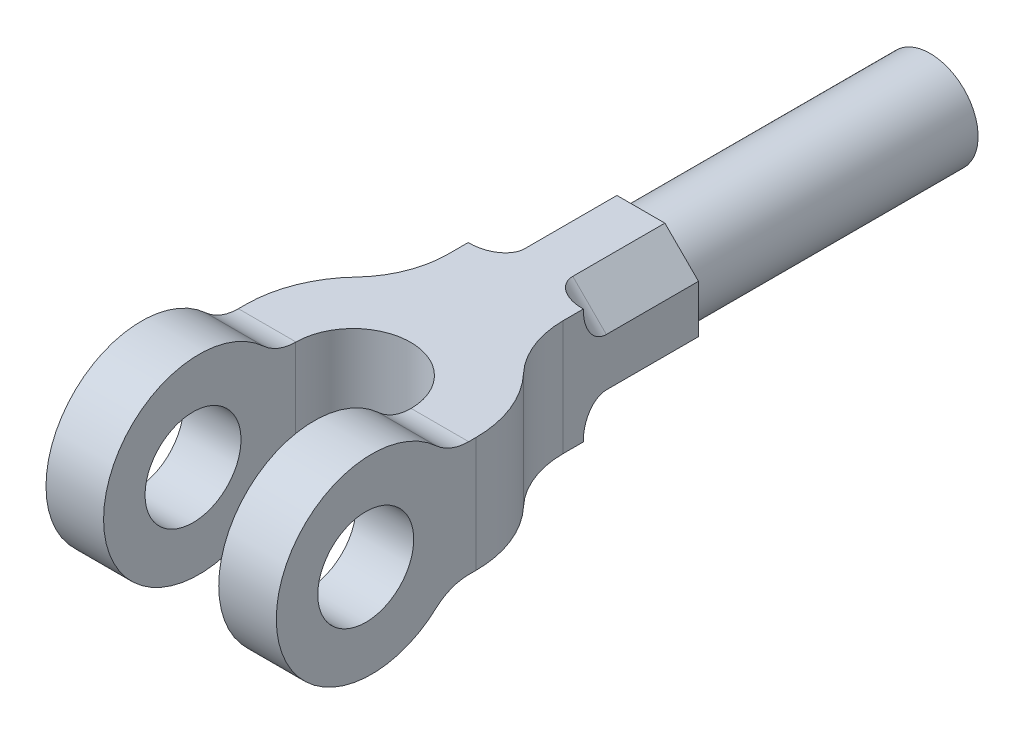
SolidWorks part; units mm, degrees
ref_plane "Front Plane" through (0, 0, 0) normal (0, 0, 1) x (1, 0, 0)
ref_plane "Top Plane" through (0, 0, 0) normal (0, 1, 0) x (1, 0, 0)
ref_plane "Right Plane" through (0, 0, 0) normal (1, 0, 0) x (0, 0, -1)
sketch "Sketch2" plane through (0, 0, 0) normal (0, 1, 0) x (1, 0, 0)
  line L1 (0, 0) -> (-120, 0)
  line L2 (0, 0) -> (0, 250)
  line L3 (0, 250) -> (-120, 250)
  line L4 (-120, 0) -> (-120, 250)
  line L5 (0, 0) -> (-120, 250) construction
  line L6 (0, 250) -> (-120, 0) construction
  point P4 (-98.6047, 60.2326)
  dimension "D1" = 250
  dimension "D2" = 120
extrude "Boss-Extrude1" add sketch "Sketch2" along normal mid plane 100
sketch "Sketch3" plane through (0, 50, 0) normal (0, 1, 0) x (1, 0, 0)
  line L0 (-60, 249.7647) -> (-60, -1.0314) construction
  line L1 (-120, 250) -> (-120, 0) construction
  line L2 (-30, 100) -> (-30, 0)
  line L4 (0, 250) -> (-120, 250) construction
  line L5 (-90, 250) -> (-90, 179.4983)
  line L6 (-30, 250) -> (-30, 179.4983)
  line L7 (-90, 100) -> (-90, 0)
  line L10 (0, 0) -> (0, 250)
  line L11 (0, 250) -> (-120, 250)
  line L12 (-120, 250) -> (-120, 0)
  line L13 (-120, 0) -> (0, 0)
  line L14 (0, 0) -> (0, 250)
  line L15 (0, 250) -> (-120, 250)
  line L16 (-120, 250) -> (-120, 0)
  line L17 (-120, 0) -> (0, 0)
  arc A0 (-103.6364, 145.1809) -> (-120, 104) centre (-60, 104) ccw
  arc A1 (-30, 100) -> (-90, 100) centre (-60, 100) ccw
  arc A2 (-30, 179.4983) -> (-16.3636, 145.1809) centre (20, 179.4983) ccw
  arc A3 (-90, 179.4983) -> (-103.6364, 145.1809) centre (-140, 179.4983) cw
  arc A4 (0, 104) -> (-16.3636, 145.1809) centre (-60, 104) ccw
  point P20 (-30, 155.9615)
  point P23 (-90, 155.9615)
  line M9 (0, 250) -> (-120, 250)
  line M10 (-120, 250) -> (-120, 0)
  line M11 (-120, 0) -> (0, 0)
  dimension "D3" = 120
  dimension "D4" = 60
  dimension "D5" = 150
  dimension "D8" = 50
  dimension "D1" = 60
  dimension "D2" = 4
  dimension "D7" = 30
  dimension "D6" = 0
extrude "Cut-Extrude1" cut sketch "Sketch3" against normal through all both and the other way through all contours A3 L5 A0 M9 M10 | A4 L14 L6 A2 M9 | A1 L0 L17 L2 | L0 A1 L7 M11 region at (-45.4324, 50, -61.9624) region at (-74.5676, 50, -61.9624) region at (-106.1748, 50, -195.5027) region at (-13.8252, 50, -195.5027)
sketch "Sketch4" plane through (0, 0, 0) normal (1, 0, 0) x (0, 0, -1)
  line L0 (0, -50) -> (104, -50) construction
  line L1 (0, 50) -> (0, -50) construction
  line L3 (-1.4536, -0.2968) -> (250.6092, -0.2968) construction
  line L5 (250, 50) -> (179.4983, 50) construction
  line L6 (89.3317, -30.2968) -> (250, -30.2968)
  line L7 (179.4983, -50) -> (250, -50) construction
  line L8 (250, -50) -> (250, 50) construction
  line L9 (179.4983, 50) -> (145.1809, 50) construction
  line L10 (145.1809, -50) -> (179.4983, -50) construction
  line L11 (104, -50) -> (145.1809, -50) construction
  line L12 (145.1809, 50) -> (104, 50) construction
  line L13 (104, 50) -> (0, 50) construction
  line L14 (250, 50) -> (179.4983, 50)
  line L15 (179.4983, -50) -> (250, -50)
  line L16 (250, -50) -> (250, 50)
  line L17 (179.4983, 50) -> (145.1809, 50)
  line L18 (145.1809, -50) -> (179.4983, -50)
  line L19 (104, -50) -> (145.1809, -50)
  line L20 (145.1809, 50) -> (104, 50)
  line L21 (0, -50) -> (104, -50)
  line L22 (104, 50) -> (0, 50)
  line L23 (0, 50) -> (0, -50)
  line L24 (89.3317, 29.7032) -> (250, 29.7032)
  circle A0 centre (49.7032, -0.2968) radius 49.7032
  line M5 (0, -50) -> (104, -50)
  line M6 (104, -50) -> (104, 50)
  line M7 (104, 50) -> (0, 50)
  line M8 (0, 50) -> (0, -50)
  dimension "D3" = 99.4065
  dimension "D1" = 30
  dimension "D2" = 30
extrude "Cut-Extrude2" cut sketch "Sketch4" against normal blind 100 contours L24 L16 L14 L17 L20 M6 | L19 L18 L15 L16 L6 M6 | A0 L21 L6 M6 | A0 L24 M6 M7 M8 | A0 L23 M5 region at (0, -42.0403, -89.1224) region at (0, -40.1484, -177) region at (0, -38.8979, -11.1021) region at (0, 39.8516, -177) region at (0, 30.8585, -96.6658)
sketch "Sketch5" plane through (0, 0, 0) normal (1, 0, 0) x (0, 0, -1)
  line L0 (145.1809, 29.7032) -> (104, 29.7032) construction
  line L1 (145.1809, 29.7032) -> (104, 29.7032)
  line L2 (89.3317, -30.2968) -> (149.4983, -30.2968) construction
  line L3 (104, 29.7032) -> (89.3317, 29.7032)
  line L4 (89.3317, -30.2968) -> (104, -30.2968)
  line L5 (104, -30.2968) -> (104, 29.7032)
  line L6 (104, 29.7032) -> (89.3317, 29.7032)
  line L7 (89.3317, -30.2968) -> (104, -30.2968)
  line L9 (89.3317, -30.2968) -> (149.4983, -30.2968)
  line L10 (149.4983, 50) -> (0, 50) construction
  line L11 (149.4983, 50) -> (0, 50)
  line L12 (0, 50) -> (0, -0.2968) construction
  line L13 (0, 50) -> (0, -0.2968)
  line L14 (0, -0.2968) -> (0, -50) construction
  line L15 (0, -0.2968) -> (0, -50)
  line L16 (0, -50) -> (49.7032, -50) construction
  line L17 (0, -50) -> (49.7032, -50)
  line L18 (49.7032, -50) -> (149.4983, -50) construction
  line L19 (49.7032, -50) -> (149.4983, -50)
  line L20 (149.4983, 50) -> (149.4983, 29.7032) construction
  line L21 (149.4983, 50) -> (149.4983, 29.7032)
  line L22 (179.4983, 29.7032) -> (145.1809, 29.7032) construction
  line L23 (149.4983, -30.2968) -> (89.3317, -30.2968)
  line L24 (49.7032, -50) -> (149.4983, -50)
  line L25 (149.4983, -50) -> (149.4983, -30.2968)
  line L26 (149.4983, -30.2968) -> (89.3317, -30.2968)
  line L27 (49.7032, -50) -> (149.4983, -50)
  line L28 (149.4983, -50) -> (149.4983, -30.2968)
  line L29 (179.4983, 29.7032) -> (145.1809, 29.7032)
  arc A0 (0, -0.2968) -> (49.7032, -50) centre (49.7032, -0.2968) ccw construction
  arc A1 (89.3317, 29.7032) -> (89.3317, -30.2968) centre (49.7032, -0.2968) ccw
  arc A2 (89.3317, 29.7032) -> (89.3317, -30.2968) centre (49.7032, -0.2968) ccw
  arc A3 (89.3317, 29.7032) -> (0, -0.2968) centre (49.7032, -0.2968) ccw construction
  arc A4 (0, -0.2968) -> (49.7032, -50) centre (49.7032, -0.2968) ccw
  arc A5 (89.3317, 29.7032) -> (0, -0.2968) centre (49.7032, -0.2968) ccw
  arc A7 (49.7032, -50) -> (89.3317, -30.2968) centre (49.7032, -0.2968) ccw
  arc A8 (49.7032, -50) -> (89.3317, -30.2968) centre (49.7032, -0.2968) ccw
  line M9 (104, 29.7032) -> (89.3317, 29.7032)
  arc M10 (89.3317, 29.7032) -> (89.3317, -30.2968) centre (49.7032, -0.2968) ccw
  line M11 (89.3317, -30.2968) -> (104, -30.2968)
  dimension "D1" = 0
  dimension "D2" = 0
extrude "Cut-Extrude3" cut sketch "Sketch5" against normal through all both and the other way through all contours L29 L21 L11 L13 L1 M10 M9 | L15 L17 M10 | L19 L28 L9 M11 M10 region at (0, 40.1577, -84.7556) region at (0, -40.8466, -112.8624) region at (0, -38.8979, -11.1021)
fillet "Fillet1" radius 25 4 edges at (-15, 29.7032, -89.3317) (-15, -30.2968, -89.3317)
sketch "Sketch6" plane through (0, 0, -250) normal (0, 0, -1) x (-1, 0, 0)
  line L0 (90, -30.2968) -> (90, 29.7032) construction
  line L1 (90, -30.2968) -> (90, 29.7032) construction
  line L2 (30, -30.2968) -> (30, 29.7032) construction
  line L3 (90, 29.7032) -> (30, 29.7032) construction
  line L4 (90, 29.7032) -> (72.5, 29.7032)
  line L5 (90, 12.2032) -> (90, 29.7032)
  line L6 (72.5, 29.7032) -> (90, 12.2032)
  line L7 (30, 12.2032) -> (47.5, 29.7032)
  line L8 (30, 29.7032) -> (30, 12.2032)
  line L9 (47.5, 29.7032) -> (30, 29.7032)
  line L10 (47.5, -30.2968) -> (30, -12.7968)
  line L11 (30, -30.2968) -> (47.5, -30.2968)
  line L12 (30, -12.7968) -> (30, -30.2968)
  line L13 (90, -12.7968) -> (72.5, -30.2968)
  line L14 (90, -30.2968) -> (90, -12.7968)
  line L15 (72.5, -30.2968) -> (90, -30.2968)
  circle A0 centre (60, -0.0449) radius 25
  line M14 (90, -30.2968) -> (90, 29.7032)
  line M15 (90, 29.7032) -> (30, 29.7032)
  line M16 (30, 29.7032) -> (30, -30.2968)
  dimension "D1" = 50
  dimension "D2" = 30
  dimension "D3" = 17.5
  dimension "D4" = 17.5
  dimension "D5" = 4
extrude "Cut-Extrude5" cut sketch "Sketch6" against normal blind 60 contours L8 L7 M15 | L6 M15 M14 | L13 L15 L14 | L11 L10 M16 region at (-84.1667, 23.8699, -250) region at (-84.1667, -24.4634, -250) region at (-35.8333, -24.4634, -250) region at (-35.8333, 23.8699, -250)
sketch "Sketch7" plane through (0, 0, -190) normal (0, 0, -1) x (-1, 0, 0)
fillet "Fillet4" radius 12 4 edges at (-81.25, -21.5468, -190) (-81.25, 20.9532, -190) (-38.75, -21.5468, -190) (-38.75, 20.9532, -190)
sketch "Sketch8" plane through (0, 0, -250) normal (0, 0, -1) x (-1, 0, 0)
  line L0 (30, -12.7968) -> (30, 12.2032) construction
  line L1 (72.5, 29.7032) -> (47.5, 29.7032) construction
  circle A0 centre (60, -0.2968) radius 25
  dimension "D2" = 50
  dimension "D1" = 30
  dimension "D3" = 30
extrude "Boss-Extrude2" add sketch "Sketch8" along normal blind 150.7
sketch "Sketch9" plane through (-120, 0, 0) normal (-1, 0, 0) x (0, 0, 1)
  circle A0 centre (-46.6099, -0.0353) radius 25
  dimension "D1" = 50
extrude "Cut-Extrude11" cut sketch "Sketch9" against normal through all both and the other way through all
